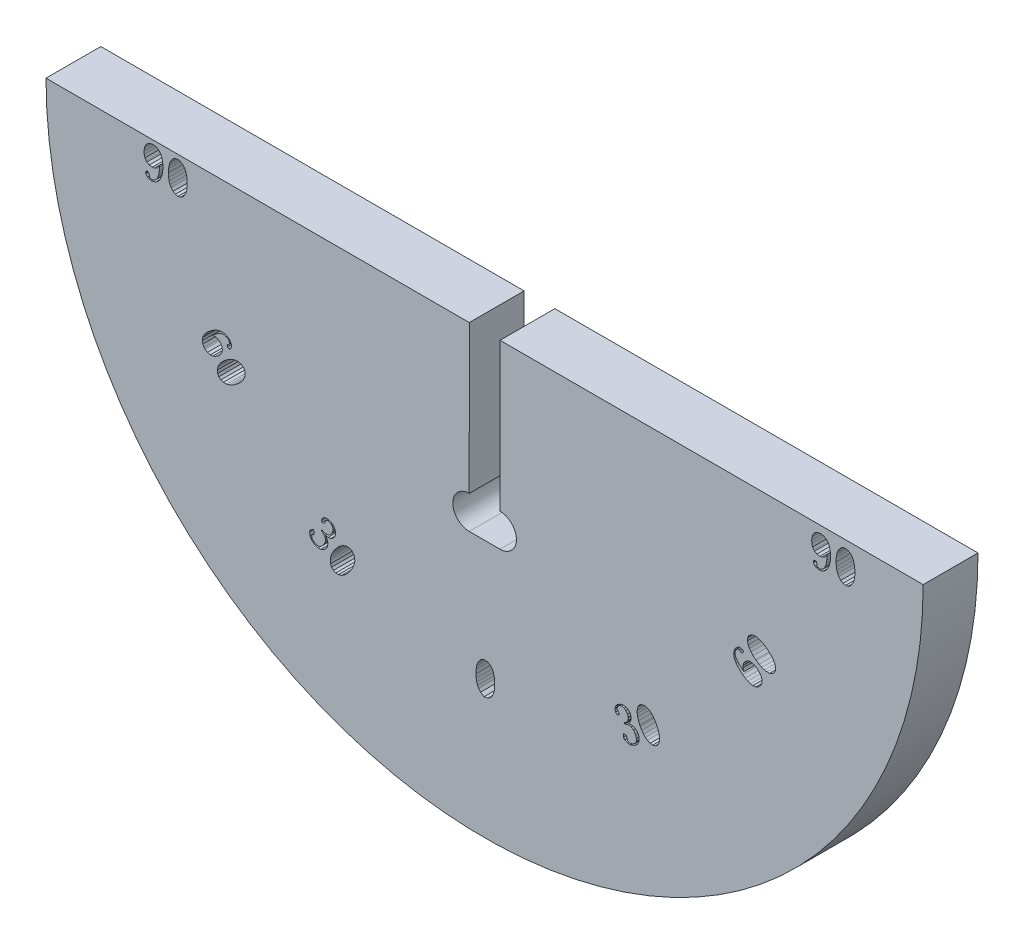
SolidWorks part; units mm, degrees
ref_plane "前视基准面" through (0, 0, 0) normal (0, 0, 1) x (1, 0, 0)
ref_plane "上视基准面" through (0, 0, 0) normal (0, 1, 0) x (1, 0, 0)
ref_plane "右视基准面" through (0, 0, 0) normal (1, 0, 0) x (0, 0, -1)
sketch "草图2" plane through (0, 0, 0) normal (0, 0, 1) x (1, 0, 0)
  line L0 (2575.9105, 4726.7519) -> (2576.0773, 4726.9587)
  line L1 (2576.0773, 4726.9587) -> (2576.1876, 4727.1913)
  line L2 (2576.1876, 4727.1913) -> (2576.2103, 4727.3332)
  line L3 (2576.2103, 4727.3332) -> (2576.169, 4727.5745)
  line L4 (2576.169, 4727.5745) -> (2576.024, 4727.8109)
  line L5 (2576.024, 4727.8109) -> (2575.9424, 4727.8993)
  line L6 (2575.9424, 4727.8993) -> (2575.7171, 4728.0289)
  line L7 (2575.7171, 4728.0289) -> (2575.5458, 4728.0673)
  line L8 (2575.5458, 4728.0673) -> (2575.2788, 4728.0401)
  line L9 (2575.2788, 4728.0401) -> (2575.4114, 4728.1448)
  line L10 (2575.4114, 4728.1448) -> (2575.6813, 4728.3434)
  line L11 (2575.6813, 4728.3434) -> (2575.9216, 4728.487)
  line L12 (2575.9216, 4728.487) -> (2576.1176, 4728.5721)
  line L13 (2576.1176, 4728.5721) -> (2576.2838, 4728.602)
  line L14 (2576.2838, 4728.602) -> (2576.3637, 4728.6027)
  line L15 (2576.3637, 4728.6027) -> (2576.6101, 4728.5404)
  line L16 (2576.6101, 4728.5404) -> (2576.8067, 4728.3818)
  line L17 (2576.8067, 4728.3818) -> (2576.8836, 4728.2111)
  line L18 (2576.8836, 4728.2111) -> (2576.8363, 4728.1095)
  line L19 (2576.8363, 4728.1095) -> (2576.7848, 4728.0671)
  line L20 (2576.7848, 4728.0671) -> (2576.7111, 4728.0242)
  line L21 (2576.7111, 4728.0242) -> (2576.6429, 4727.9261)
  line L22 (2576.6429, 4727.9261) -> (2576.6846, 4727.7908)
  line L23 (2576.6846, 4727.7908) -> (2576.8089, 4727.7216)
  line L24 (2576.8089, 4727.7216) -> (2576.9452, 4727.7895)
  line L25 (2576.9452, 4727.7895) -> (2576.9559, 4727.7943)
  line L26 (2576.9559, 4727.7943) -> (2577.0444, 4728.0395)
  line L27 (2577.0444, 4728.0395) -> (2577.0279, 4728.183)
  line L28 (2577.0279, 4728.183) -> (2576.9052, 4728.4198)
  line L29 (2576.9052, 4728.4198) -> (2576.8236, 4728.5082)
  line L30 (2576.8236, 4728.5082) -> (2576.6226, 4728.6551)
  line L31 (2576.6226, 4728.6551) -> (2576.3874, 4728.7354)
  line L32 (2576.3874, 4728.7354) -> (2576.1181, 4728.7489)
  line L33 (2576.1181, 4728.7489) -> (2575.9718, 4728.7246)
  line L34 (2575.9718, 4728.7246) -> (2575.7478, 4728.659)
  line L35 (2575.7478, 4728.659) -> (2575.513, 4728.5532)
  line L36 (2575.513, 4728.5532) -> (2575.2713, 4728.4058)
  line L37 (2575.2713, 4728.4058) -> (2575.0241, 4728.2206)
  line L38 (2575.0241, 4728.2206) -> (2574.8147, 4728.03)
  line L39 (2574.8147, 4728.03) -> (2574.6271, 4727.8267)
  line L40 (2574.6271, 4727.8267) -> (2574.4956, 4727.6198)
  line L41 (2574.4956, 4727.6198) -> (2574.4102, 4727.4176)
  line L42 (2574.4102, 4727.4176) -> (2574.4082, 4727.4007)
  line L43 (2574.4082, 4727.4007) -> (2574.3729, 4727.1441)
  line L44 (2574.3729, 4727.1441) -> (2574.4249, 4726.9075)
  line L45 (2574.4249, 4726.9075) -> (2574.5598, 4726.6794)
  line L46 (2574.5598, 4726.6794) -> (2574.639, 4726.5963)
  line L47 (2574.639, 4726.5963) -> (2574.8497, 4726.4634)
  line L48 (2574.8497, 4726.4634) -> (2575.113, 4726.3991)
  line L49 (2575.113, 4726.3991) -> (2575.1222, 4726.4)
  line L50 (2575.1222, 4726.4) -> (2575.3456, 4726.4172)
  line L51 (2575.3456, 4726.4172) -> (2575.5798, 4726.5099)
  line L52 (2575.5798, 4726.5099) -> (2575.8303, 4726.6805)
  line L53 (2575.8303, 4726.6805) -> (2575.9105, 4726.7519)
  line L54 (2574.6009, 4727.2666) -> (2574.7043, 4727.4699)
  line L55 (2574.7043, 4727.4699) -> (2574.862, 4727.6758)
  line L56 (2574.862, 4727.6758) -> (2575.0864, 4727.8828)
  line L57 (2575.0864, 4727.8828) -> (2575.3661, 4727.9318)
  line L58 (2575.3661, 4727.9318) -> (2575.5985, 4727.9145)
  line L59 (2575.5985, 4727.9145) -> (2575.6938, 4727.874)
  line L60 (2575.6938, 4727.874) -> (2575.8953, 4727.7048)
  line L61 (2575.8953, 4727.7048) -> (2575.9627, 4727.5907)
  line L62 (2575.9627, 4727.5907) -> (2575.9667, 4727.3325)
  line L63 (2575.9667, 4727.3325) -> (2575.9632, 4727.3117)
  line L64 (2575.9632, 4727.3117) -> (2575.8588, 4727.0946)
  line L65 (2575.8588, 4727.0946) -> (2575.662, 4726.8903)
  line L66 (2575.662, 4726.8903) -> (2575.4566, 4726.7336)
  line L67 (2575.4566, 4726.7336) -> (2575.2207, 4726.6017)
  line L68 (2575.2207, 4726.6017) -> (2575.0326, 4726.549)
  line L69 (2575.0326, 4726.549) -> (2574.8569, 4726.5757)
  line L70 (2574.8569, 4726.5757) -> (2574.6496, 4726.7295)
  line L71 (2574.6496, 4726.7295) -> (2574.6284, 4726.7552)
  line L72 (2574.6284, 4726.7552) -> (2574.5497, 4726.9798)
  line L73 (2574.5497, 4726.9798) -> (2574.6009, 4727.2666)
  line L74 (2575.9736, 4725.1533) -> (2575.9249, 4725.3879)
  line L75 (2575.9249, 4725.3879) -> (2576.0096, 4725.67)
  line L76 (2576.0096, 4725.67) -> (2576.0968, 4725.8184)
  line L77 (2576.0968, 4725.8184) -> (2576.2408, 4726.0117)
  line L78 (2576.2408, 4726.0117) -> (2576.4323, 4726.2135)
  line L79 (2576.4323, 4726.2135) -> (2576.666, 4726.4215)
  line L80 (2576.666, 4726.4215) -> (2576.8457, 4726.557)
  line L81 (2576.8457, 4726.557) -> (2577.0811, 4726.7112)
  line L82 (2577.0811, 4726.7112) -> (2577.3072, 4726.8292)
  line L83 (2577.3072, 4726.8292) -> (2577.5211, 4726.9031)
  line L84 (2577.5211, 4726.9031) -> (2577.5885, 4726.9174)
  line L85 (2577.5885, 4726.9174) -> (2577.8651, 4726.9232)
  line L86 (2577.8651, 4726.9232) -> (2578.0454, 4726.8151)
  line L87 (2578.0454, 4726.8151) -> (2578.0873, 4726.7505)
  line L88 (2578.0873, 4726.7505) -> (2578.1321, 4726.53)
  line L89 (2578.1321, 4726.53) -> (2578.0378, 4726.2692)
  line L90 (2578.0378, 4726.2692) -> (2577.9555, 4726.1455)
  line L91 (2577.9555, 4726.1455) -> (2577.7999, 4725.9566)
  line L92 (2577.7999, 4725.9566) -> (2577.6059, 4725.7601)
  line L93 (2577.6059, 4725.7601) -> (2577.3737, 4725.556)
  line L94 (2577.3737, 4725.556) -> (2577.179, 4725.4041)
  line L95 (2577.179, 4725.4041) -> (2576.9421, 4725.246)
  line L96 (2576.9421, 4725.246) -> (2576.7198, 4725.1266)
  line L97 (2576.7198, 4725.1266) -> (2576.5191, 4725.0522)
  line L98 (2576.5191, 4725.0522) -> (2576.4449, 4725.0316)
  line L99 (2576.4449, 4725.0316) -> (2576.1775, 4725.0267)
  line L100 (2576.1775, 4725.0267) -> (2575.9736, 4725.1533)
  line L101 (2578.1501, 4726.8968) -> (2577.9595, 4727.0556)
  line L102 (2577.9595, 4727.0556) -> (2577.7267, 4727.1305)
  line L103 (2577.7267, 4727.1305) -> (2577.4487, 4727.1208)
  line L104 (2577.4487, 4727.1208) -> (2577.4172, 4727.1194)
  line L105 (2577.4172, 4727.1194) -> (2577.1884, 4727.0645)
  line L106 (2577.1884, 4727.0645) -> (2576.9565, 4726.9664)
  line L107 (2576.9565, 4726.9664) -> (2576.7192, 4726.8306)
  line L108 (2576.7192, 4726.8306) -> (2576.4788, 4726.6517)
  line L109 (2576.4788, 4726.6517) -> (2576.4099, 4726.5982)
  line L110 (2576.4099, 4726.5982) -> (2576.1893, 4726.3897)
  line L111 (2576.1893, 4726.3897) -> (2576.0147, 4726.1858)
  line L112 (2576.0147, 4726.1858) -> (2575.8832, 4725.979)
  line L113 (2575.8832, 4725.979) -> (2575.7963, 4725.7729)
  line L114 (2575.7963, 4725.7729) -> (2575.7451, 4725.5091)
  line L115 (2575.7451, 4725.5091) -> (2575.7757, 4725.2629)
  line L116 (2575.7757, 4725.2629) -> (2575.8918, 4725.0552)
  line L117 (2575.8918, 4725.0552) -> (2576.0729, 4724.9025)
  line L118 (2576.0729, 4724.9025) -> (2576.3057, 4724.8276)
  line L119 (2576.3057, 4724.8276) -> (2576.59, 4724.8306)
  line L120 (2576.59, 4724.8306) -> (2576.6283, 4724.8382)
  line L121 (2576.6283, 4724.8382) -> (2576.8494, 4724.8961)
  line L122 (2576.8494, 4724.8961) -> (2577.0774, 4724.9956)
  line L123 (2577.0774, 4724.9956) -> (2577.3176, 4725.1391)
  line L124 (2577.3176, 4725.1391) -> (2577.5648, 4725.3243)
  line L125 (2577.5648, 4725.3243) -> (2577.6095, 4725.3605)
  line L126 (2577.6095, 4725.3605) -> (2577.8339, 4725.5675)
  line L127 (2577.8339, 4725.5675) -> (2578.0138, 4725.7738)
  line L128 (2578.0138, 4725.7738) -> (2578.1477, 4725.9753)
  line L129 (2578.1477, 4725.9753) -> (2578.2424, 4726.1784)
  line L130 (2578.2424, 4726.1784) -> (2578.2951, 4726.4461)
  line L131 (2578.2951, 4726.4461) -> (2578.2629, 4726.6884)
  line L132 (2578.2629, 4726.6884) -> (2578.1501, 4726.8968)
  line L133 (2560.123, 4740.7565) -> (2640.123, 4740.7565)
  line L134 (2600.123, 4722.8084) -> (2600.123, 4716.8788)
  line L135 (2601.5305, 4740.7565) -> (2601.523, 4727.2576)
  line L136 (2598.7261, 4740.7565) -> (2598.723, 4727.2576)
  line L137 (2560.123, 4740.7565) -> (2570.123, 4740.7565)
  line L138 (2560.7307, 4733.8105) -> (2570.5787, 4735.547)
  line L139 (2562.5353, 4727.0757) -> (2571.9322, 4730.4959)
  line L140 (2565.482, 4720.7565) -> (2574.1422, 4725.7565)
  line L141 (2569.4812, 4715.045) -> (2577.1416, 4721.4728)
  line L142 (2574.4115, 4710.1147) -> (2580.8394, 4717.7751)
  line L143 (2580.123, 4706.1155) -> (2585.123, 4714.7757)
  line L144 (2586.4422, 4703.1688) -> (2589.8624, 4712.5657)
  line L145 (2593.1771, 4701.3642) -> (2594.9135, 4711.2122)
  line L146 (2600.123, 4700.7565) -> (2600.123, 4710.7565)
  line L147 (2607.0689, 4701.3642) -> (2605.3324, 4711.2122)
  line L148 (2613.6331, 4703.6378) -> (2610.3836, 4712.5657)
  line L149 (2620.123, 4706.1155) -> (2615.123, 4714.7757)
  line L150 (2625.8345, 4710.1147) -> (2619.4066, 4717.7751)
  line L151 (2630.7648, 4715.045) -> (2623.1043, 4721.4728)
  line L152 (2634.764, 4720.7565) -> (2626.1037, 4725.7565)
  line L153 (2637.7107, 4727.0757) -> (2628.3138, 4730.4959)
  line L154 (2639.5153, 4733.8105) -> (2629.6672, 4735.547)
  line L155 (2640.123, 4740.7565) -> (2630.123, 4740.7565)
  line L156 (2560.123, 4740.7565) -> (2565.123, 4740.7565)
  line L157 (2560.1473, 4739.3605) -> (2565.1443, 4739.535)
  line L158 (2560.2204, 4737.9662) -> (2565.2082, 4738.315)
  line L159 (2560.3421, 4736.5753) -> (2565.3147, 4737.098)
  line L160 (2560.5123, 4735.1895) -> (2565.4636, 4735.8854)
  line L161 (2560.7307, 4733.8105) -> (2565.6547, 4734.6788)
  line L162 (2560.9971, 4732.44) -> (2565.8878, 4733.4796)
  line L163 (2561.3112, 4731.0796) -> (2566.1626, 4732.2892)
  line L164 (2561.6725, 4729.731) -> (2566.4788, 4731.1092)
  line L165 (2562.0807, 4728.3958) -> (2566.836, 4729.9409)
  line L166 (2562.5353, 4727.0757) -> (2567.2337, 4728.7858)
  line L167 (2563.0356, 4725.7722) -> (2567.6715, 4727.6452)
  line L168 (2563.5812, 4724.487) -> (2568.1489, 4726.5207)
  line L169 (2564.1712, 4723.2216) -> (2568.6652, 4725.4135)
  line L170 (2564.8051, 4721.9776) -> (2569.2198, 4724.325)
  line L171 (2565.482, 4720.7565) -> (2569.8121, 4723.2565)
  line L172 (2566.2011, 4719.5597) -> (2570.4413, 4722.2093)
  line L173 (2566.9615, 4718.3888) -> (2571.1067, 4721.1847)
  line L174 (2567.7623, 4717.2451) -> (2571.8074, 4720.184)
  line L175 (2568.6025, 4716.13) -> (2572.5426, 4719.2083)
  line L176 (2569.4812, 4715.045) -> (2573.3114, 4718.2589)
  line L177 (2570.3972, 4713.9912) -> (2574.1129, 4717.3369)
  line L178 (2571.3494, 4712.9701) -> (2574.9461, 4716.4434)
  line L179 (2572.3366, 4711.9829) -> (2575.8099, 4715.5796)
  line L180 (2573.3578, 4711.0307) -> (2576.7034, 4714.7464)
  line L181 (2574.4115, 4710.1147) -> (2577.6254, 4713.9449)
  line L182 (2575.4965, 4709.236) -> (2578.5748, 4713.1761)
  line L183 (2576.6116, 4708.3958) -> (2579.5505, 4712.4409)
  line L184 (2577.7553, 4707.595) -> (2580.5512, 4711.7402)
  line L185 (2578.9262, 4706.8346) -> (2581.5758, 4711.0748)
  line L186 (2580.123, 4706.1155) -> (2582.623, 4710.4456)
  line L187 (2581.3441, 4705.4386) -> (2583.6915, 4709.8533)
  line L188 (2582.5881, 4704.8047) -> (2584.78, 4709.2987)
  line L189 (2583.8535, 4704.2147) -> (2585.8872, 4708.7824)
  line L190 (2585.1387, 4703.6691) -> (2587.0117, 4708.305)
  line L191 (2586.4422, 4703.1688) -> (2588.1523, 4707.8672)
  line L192 (2587.7623, 4702.7142) -> (2589.3074, 4707.4695)
  line L193 (2589.0975, 4702.306) -> (2590.4757, 4707.1123)
  line L194 (2590.4461, 4701.9446) -> (2591.6557, 4706.7961)
  line L195 (2591.8065, 4701.6306) -> (2592.8461, 4706.5213)
  line L196 (2593.1771, 4701.3642) -> (2594.0453, 4706.2882)
  line L197 (2594.5561, 4701.1458) -> (2595.2519, 4706.0971)
  line L198 (2595.9418, 4700.9756) -> (2596.4645, 4705.9482)
  line L199 (2597.3327, 4700.8539) -> (2597.6815, 4705.8417)
  line L200 (2598.727, 4700.7808) -> (2598.9015, 4705.7778)
  line L201 (2600.123, 4700.7565) -> (2600.123, 4705.7565)
  line L202 (2601.519, 4700.7808) -> (2601.3445, 4705.7778)
  line L203 (2602.9132, 4700.8539) -> (2602.5645, 4705.8417)
  line L204 (2604.3041, 4700.9756) -> (2603.7815, 4705.9482)
  line L205 (2605.6899, 4701.1458) -> (2604.994, 4706.0971)
  line L206 (2607.0689, 4701.3642) -> (2606.2007, 4706.2882)
  line L207 (2608.4394, 4701.6306) -> (2607.3999, 4706.5213)
  line L208 (2609.7999, 4701.9446) -> (2608.5902, 4706.7961)
  line L209 (2611.1485, 4702.306) -> (2609.7703, 4707.1123)
  line L210 (2612.4837, 4702.7142) -> (2610.9386, 4707.4695)
  line L211 (2613.6331, 4703.6378) -> (2612.0937, 4707.8672)
  line L212 (2614.97, 4704.0571) -> (2613.2342, 4708.305)
  line L213 (2616.2208, 4704.6812) -> (2614.3588, 4708.7824)
  line L214 (2617.6578, 4704.8047) -> (2615.466, 4709.2987)
  line L215 (2618.9018, 4705.4386) -> (2616.5545, 4709.8533)
  line L216 (2620.123, 4706.1155) -> (2617.623, 4710.4456)
  line L217 (2621.3198, 4706.8346) -> (2618.6702, 4711.0748)
  line L218 (2622.4907, 4707.595) -> (2619.6947, 4711.7402)
  line L219 (2623.6344, 4708.3958) -> (2620.6955, 4712.4409)
  line L220 (2624.7494, 4709.236) -> (2621.6711, 4713.1761)
  line L221 (2625.8345, 4710.1147) -> (2622.6205, 4713.9449)
  line L222 (2626.8882, 4711.0307) -> (2623.5426, 4714.7464)
  line L223 (2627.9093, 4711.9829) -> (2624.436, 4715.5796)
  line L224 (2628.8966, 4712.9701) -> (2625.2999, 4716.4434)
  line L225 (2629.8488, 4713.9912) -> (2626.133, 4717.3369)
  line L226 (2630.7648, 4715.045) -> (2626.9345, 4718.2589)
  line L227 (2631.6434, 4716.13) -> (2627.7034, 4719.2083)
  line L228 (2632.4837, 4717.2451) -> (2628.4386, 4720.184)
  line L229 (2633.2845, 4718.3888) -> (2629.1393, 4721.1847)
  line L230 (2634.0449, 4719.5597) -> (2629.8047, 4722.2093)
  line L231 (2634.764, 4720.7565) -> (2630.4339, 4723.2565)
  line L232 (2635.4409, 4721.9776) -> (2631.0261, 4724.325)
  line L233 (2636.0747, 4723.2216) -> (2631.5808, 4725.4135)
  line L234 (2636.6648, 4724.487) -> (2632.0971, 4726.5207)
  line L235 (2637.2103, 4725.7722) -> (2632.5744, 4727.6452)
  line L236 (2637.7107, 4727.0757) -> (2633.0122, 4728.7858)
  line L237 (2638.1652, 4728.3958) -> (2633.41, 4729.9409)
  line L238 (2638.5734, 4729.731) -> (2633.7671, 4731.1092)
  line L239 (2638.9348, 4731.0796) -> (2634.0833, 4732.2892)
  line L240 (2639.2489, 4732.44) -> (2634.3581, 4733.4796)
  line L241 (2639.5153, 4733.8105) -> (2634.5913, 4734.6788)
  line L242 (2639.7337, 4735.1895) -> (2634.7824, 4735.8854)
  line L243 (2639.9039, 4736.5753) -> (2634.9312, 4737.098)
  line L244 (2640.0255, 4737.9662) -> (2635.0377, 4738.315)
  line L245 (2640.0986, 4739.3605) -> (2635.1017, 4739.535)
  line L246 (2640.123, 4740.7565) -> (2635.123, 4740.7565)
  line L247 (2572.133, 4737.564) -> (2571.9203, 4737.6796)
  line L248 (2571.9203, 4737.6796) -> (2571.7547, 4737.9238)
  line L249 (2571.7547, 4737.9238) -> (2571.6926, 4738.0811)
  line L250 (2571.6926, 4738.0811) -> (2571.6347, 4738.317)
  line L251 (2571.6347, 4738.317) -> (2571.6016, 4738.5901)
  line L252 (2571.6016, 4738.5901) -> (2571.5892, 4738.9046)
  line L253 (2571.5892, 4738.9046) -> (2571.5933, 4739.1281)
  line L254 (2571.5933, 4739.1281) -> (2571.6223, 4739.4095)
  line L255 (2571.6223, 4739.4095) -> (2571.6761, 4739.6578)
  line L256 (2571.6761, 4739.6578) -> (2571.7547, 4739.873)
  line L257 (2571.7547, 4739.873) -> (2571.7878, 4739.9351)
  line L258 (2571.7878, 4739.9351) -> (2571.9575, 4740.1503)
  line L259 (2571.9575, 4740.1503) -> (2572.1562, 4740.2207)
  line L260 (2572.1562, 4740.2207) -> (2572.2307, 4740.2165)
  line L261 (2572.2307, 4740.2165) -> (2572.4293, 4740.1089)
  line L262 (2572.4293, 4740.1089) -> (2572.57, 4739.873)
  line L263 (2572.57, 4739.873) -> (2572.6155, 4739.7282)
  line L264 (2572.6155, 4739.7282) -> (2572.6652, 4739.4882)
  line L265 (2572.6652, 4739.4882) -> (2572.6942, 4739.215)
  line L266 (2572.6942, 4739.215) -> (2572.7024, 4738.9046)
  line L267 (2572.7024, 4738.9046) -> (2572.6983, 4738.6605)
  line L268 (2572.6983, 4738.6605) -> (2572.6693, 4738.3749)
  line L269 (2572.6693, 4738.3749) -> (2572.6238, 4738.1266)
  line L270 (2572.6238, 4738.1266) -> (2572.5535, 4737.9238)
  line L271 (2572.5535, 4737.9238) -> (2572.5204, 4737.8534)
  line L272 (2572.5204, 4737.8534) -> (2572.3589, 4737.6424)
  line L273 (2572.3589, 4737.6424) -> (2572.133, 4737.564)
  line L274 (2572.9861, 4738.4492) -> (2573.0046, 4738.9046)
  line L275 (2573.0046, 4738.9046) -> (2573.0046, 4738.9667)
  line L276 (2573.0046, 4738.9667) -> (2572.9839, 4739.2688)
  line L277 (2572.9839, 4739.2688) -> (2572.9383, 4739.5378)
  line L278 (2572.9383, 4739.5378) -> (2572.868, 4739.7737)
  line L279 (2572.868, 4739.7737) -> (2572.7687, 4739.9724)
  line L280 (2572.7687, 4739.9724) -> (2572.5948, 4740.1793)
  line L281 (2572.5948, 4740.1793) -> (2572.3879, 4740.3117)
  line L282 (2572.3879, 4740.3117) -> (2572.1562, 4740.3573)
  line L283 (2572.1562, 4740.3573) -> (2572.1479, 4740.3573)
  line L284 (2572.1479, 4740.3573) -> (2571.912, 4740.3117)
  line L285 (2571.912, 4740.3117) -> (2571.7092, 4740.1752)
  line L286 (2571.7092, 4740.1752) -> (2571.5395, 4739.9558)
  line L287 (2571.5395, 4739.9558) -> (2571.523, 4739.9269)
  line L288 (2571.523, 4739.9269) -> (2571.4195, 4739.7158)
  line L289 (2571.4195, 4739.7158) -> (2571.345, 4739.4757)
  line L290 (2571.345, 4739.4757) -> (2571.3036, 4739.2067)
  line L291 (2571.3036, 4739.2067) -> (2571.2871, 4738.9046)
  line L292 (2571.2871, 4738.9046) -> (2571.2912, 4738.8177)
  line L293 (2571.2912, 4738.8177) -> (2571.3119, 4738.5156)
  line L294 (2571.3119, 4738.5156) -> (2571.3574, 4738.2507)
  line L295 (2571.3574, 4738.2507) -> (2571.4361, 4738.019)
  line L296 (2571.4361, 4738.019) -> (2571.5395, 4737.8245)
  line L297 (2571.5395, 4737.8245) -> (2571.7133, 4737.6134)
  line L298 (2571.7133, 4737.6134) -> (2571.9203, 4737.4851)
  line L299 (2571.9203, 4737.4851) -> (2572.1562, 4737.4396)
  line L300 (2572.1562, 4737.4396) -> (2572.3879, 4737.4851)
  line L301 (2572.3879, 4737.4851) -> (2572.5907, 4737.6175)
  line L302 (2572.5907, 4737.6175) -> (2572.7687, 4737.841)
  line L303 (2572.7687, 4737.841) -> (2572.7894, 4737.8741)
  line L304 (2572.7894, 4737.8741) -> (2572.8845, 4738.0811)
  line L305 (2572.8845, 4738.0811) -> (2572.9861, 4738.4492)
  line L306 (2584.4854, 4717.3007) -> (2584.2298, 4717.1204)
  line L307 (2584.2298, 4717.1204) -> (2584.1619, 4716.951)
  line L308 (2584.1619, 4716.951) -> (2584.1896, 4716.6819)
  line L309 (2584.1896, 4716.6819) -> (2584.1972, 4716.6568)
  line L310 (2584.1972, 4716.6568) -> (2584.319, 4716.4338)
  line L311 (2584.319, 4716.4338) -> (2584.519, 4716.2508)
  line L312 (2584.519, 4716.2508) -> (2584.6998, 4716.1453)
  line L313 (2584.6998, 4716.1453) -> (2584.9418, 4716.0679)
  line L314 (2584.9418, 4716.0679) -> (2585.1828, 4716.0707)
  line L315 (2585.1828, 4716.0707) -> (2585.2922, 4716.1023)
  line L316 (2585.2922, 4716.1023) -> (2585.5234, 4716.2198)
  line L317 (2585.5234, 4716.2198) -> (2585.6977, 4716.4035)
  line L318 (2585.6977, 4716.4035) -> (2585.7809, 4716.5584)
  line L319 (2585.7809, 4716.5584) -> (2585.8291, 4716.8203)
  line L320 (2585.8291, 4716.8203) -> (2585.8258, 4716.904)
  line L321 (2585.8258, 4716.904) -> (2585.7646, 4717.1344)
  line L322 (2585.7646, 4717.1344) -> (2585.6165, 4717.3946)
  line L323 (2585.6165, 4717.3946) -> (2585.8554, 4717.3503)
  line L324 (2585.8554, 4717.3503) -> (2586.099, 4717.3854)
  line L325 (2586.099, 4717.3854) -> (2586.2574, 4717.4769)
  line L326 (2586.2574, 4717.4769) -> (2586.4428, 4717.6735)
  line L327 (2586.4428, 4717.6735) -> (2586.5248, 4717.8731)
  line L328 (2586.5248, 4717.8731) -> (2586.5245, 4718.1464)
  line L329 (2586.5245, 4718.1464) -> (2586.5124, 4718.2138)
  line L330 (2586.5124, 4718.2138) -> (2586.4031, 4718.4406)
  line L331 (2586.4031, 4718.4406) -> (2586.2123, 4718.625)
  line L332 (2586.2123, 4718.625) -> (2586.2065, 4718.626)
  line L333 (2586.2065, 4718.626) -> (2585.9691, 4718.7473)
  line L334 (2585.9691, 4718.7473) -> (2585.7143, 4718.7853)
  line L335 (2585.7143, 4718.7853) -> (2585.4883, 4718.7323)
  line L336 (2585.4883, 4718.7323) -> (2585.2997, 4718.5689)
  line L337 (2585.2997, 4718.5689) -> (2585.2496, 4718.3816)
  line L338 (2585.2496, 4718.3816) -> (2585.3167, 4718.272)
  line L339 (2585.3167, 4718.272) -> (2585.4402, 4718.2477)
  line L340 (2585.4402, 4718.2477) -> (2585.5447, 4718.3365)
  line L341 (2585.5447, 4718.3365) -> (2585.563, 4718.4254)
  line L342 (2585.563, 4718.4254) -> (2585.64, 4718.5962)
  line L343 (2585.64, 4718.5962) -> (2585.8551, 4718.6719)
  line L344 (2585.8551, 4718.6719) -> (2586.1009, 4718.5819)
  line L345 (2586.1009, 4718.5819) -> (2586.2353, 4718.4488)
  line L346 (2586.2353, 4718.4488) -> (2586.3103, 4718.2131)
  line L347 (2586.3103, 4718.2131) -> (2586.2814, 4718.0459)
  line L348 (2586.2814, 4718.0459) -> (2586.1684, 4717.8041)
  line L349 (2586.1684, 4717.8041) -> (2586.0042, 4717.6275)
  line L350 (2586.0042, 4717.6275) -> (2585.7866, 4717.5196)
  line L351 (2585.7866, 4717.5196) -> (2585.7808, 4717.5206)
  line L352 (2585.7808, 4717.5206) -> (2585.5462, 4717.5374)
  line L353 (2585.5462, 4717.5374) -> (2585.2938, 4717.6582)
  line L354 (2585.2938, 4717.6582) -> (2585.2385, 4717.5787)
  line L355 (2585.2385, 4717.5787) -> (2585.3616, 4717.4832)
  line L356 (2585.3616, 4717.4832) -> (2585.5471, 4717.2848)
  line L357 (2585.5471, 4717.2848) -> (2585.6257, 4717.0871)
  line L358 (2585.6257, 4717.0871) -> (2585.5964, 4716.8486)
  line L359 (2585.5964, 4716.8486) -> (2585.4708, 4716.6031)
  line L360 (2585.4708, 4716.6031) -> (2585.4276, 4716.5422)
  line L361 (2585.4276, 4716.5422) -> (2585.2321, 4716.3384)
  line L362 (2585.2321, 4716.3384) -> (2585.0361, 4716.2357)
  line L363 (2585.0361, 4716.2357) -> (2584.8008, 4716.2318)
  line L364 (2584.8008, 4716.2318) -> (2584.5485, 4716.3526)
  line L365 (2584.5485, 4716.3526) -> (2584.538, 4716.3604)
  line L366 (2584.538, 4716.3604) -> (2584.3674, 4716.5591)
  line L367 (2584.3674, 4716.5591) -> (2584.3537, 4716.7723)
  line L368 (2584.3537, 4716.7723) -> (2584.4471, 4716.8483)
  line L369 (2584.4471, 4716.8483) -> (2584.5603, 4716.9534)
  line L370 (2584.5603, 4716.9534) -> (2584.5975, 4717.0658)
  line L371 (2584.5975, 4717.0658) -> (2584.4854, 4717.3007)
  line L372 (2587.5338, 4717.4909) -> (2587.2663, 4717.4035)
  line L373 (2587.2663, 4717.4035) -> (2587.2378, 4717.3935)
  line L374 (2587.2378, 4717.3935) -> (2587.0331, 4717.2745)
  line L375 (2587.0331, 4717.2745) -> (2586.834, 4717.1188)
  line L376 (2586.834, 4717.1188) -> (2586.6486, 4716.9222)
  line L377 (2586.6486, 4716.9222) -> (2586.4619, 4716.6842)
  line L378 (2586.4619, 4716.6842) -> (2586.4143, 4716.6152)
  line L379 (2586.4143, 4716.6152) -> (2586.2593, 4716.3539)
  line L380 (2586.2593, 4716.3539) -> (2586.1453, 4716.1064)
  line L381 (2586.1453, 4716.1064) -> (2586.0756, 4715.8749)
  line L382 (2586.0756, 4715.8749) -> (2586.0492, 4715.6537)
  line L383 (2586.0492, 4715.6537) -> (2586.0736, 4715.3823)
  line L384 (2586.0736, 4715.3823) -> (2586.1714, 4715.1575)
  line L385 (2586.1714, 4715.1575) -> (2586.3378, 4714.9862)
  line L386 (2586.3378, 4714.9862) -> (2586.5527, 4714.8896)
  line L387 (2586.5527, 4714.8896) -> (2586.7985, 4714.8858)
  line L388 (2586.7985, 4714.8858) -> (2587.0732, 4714.963)
  line L389 (2587.0732, 4714.963) -> (2587.106, 4714.9811)
  line L390 (2587.106, 4714.9811) -> (2587.3016, 4715.0988)
  line L391 (2587.3016, 4715.0988) -> (2587.495, 4715.2554)
  line L392 (2587.495, 4715.2554) -> (2587.6848, 4715.4602)
  line L393 (2587.6848, 4715.4602) -> (2587.8701, 4715.7073)
  line L394 (2587.8701, 4715.7073) -> (2587.9055, 4715.7577)
  line L395 (2587.9055, 4715.7577) -> (2588.0629, 4716.0155)
  line L396 (2588.0629, 4716.0155) -> (2588.1793, 4716.2597)
  line L397 (2588.1793, 4716.2597) -> (2588.2558, 4716.496)
  line L398 (2588.2558, 4716.496) -> (2588.2879, 4716.7161)
  line L399 (2588.2879, 4716.7161) -> (2588.2659, 4716.9842)
  line L400 (2588.2659, 4716.9842) -> (2588.1715, 4717.2114)
  line L401 (2588.1715, 4717.2114) -> (2588.0018, 4717.3803)
  line L402 (2588.0018, 4717.3803) -> (2587.997, 4717.3871)
  line L403 (2587.997, 4717.3871) -> (2587.7786, 4717.4813)
  line L404 (2587.7786, 4717.4813) -> (2587.5338, 4717.4909)
  line L405 (2586.3881, 4715.1017) -> (2586.282, 4715.3165)
  line L406 (2586.282, 4715.3165) -> (2586.2857, 4715.6129)
  line L407 (2586.2857, 4715.6129) -> (2586.3227, 4715.7758)
  line L408 (2586.3227, 4715.7758) -> (2586.4097, 4716.0042)
  line L409 (2586.4097, 4716.0042) -> (2586.5411, 4716.2488)
  line L410 (2586.5411, 4716.2488) -> (2586.7087, 4716.5139)
  line L411 (2586.7087, 4716.5139) -> (2586.8406, 4716.693)
  line L412 (2586.8406, 4716.693) -> (2587.0266, 4716.9103)
  line L413 (2587.0266, 4716.9103) -> (2587.2105, 4717.0805)
  line L414 (2587.2105, 4717.0805) -> (2587.3965, 4717.2117)
  line L415 (2587.3965, 4717.2117) -> (2587.4587, 4717.2455)
  line L416 (2587.4587, 4717.2455) -> (2587.7219, 4717.3247)
  line L417 (2587.7219, 4717.3247) -> (2587.9265, 4717.2716)
  line L418 (2587.9265, 4717.2716) -> (2587.984, 4717.226)
  line L419 (2587.984, 4717.226) -> (2588.0857, 4717.0243)
  line L420 (2588.0857, 4717.0243) -> (2588.0677, 4716.7482)
  line L421 (2588.0677, 4716.7482) -> (2588.0221, 4716.6047)
  line L422 (2588.0221, 4716.6047) -> (2587.9236, 4716.3782)
  line L423 (2587.9236, 4716.3782) -> (2587.7956, 4716.136)
  line L424 (2587.7956, 4716.136) -> (2587.6233, 4715.8777)
  line L425 (2587.6233, 4715.8777) -> (2587.4792, 4715.6799)
  line L426 (2587.4792, 4715.6799) -> (2587.2956, 4715.4592)
  line L427 (2587.2956, 4715.4592) -> (2587.1141, 4715.2856)
  line L428 (2587.1141, 4715.2856) -> (2586.943, 4715.1548)
  line L429 (2586.943, 4715.1548) -> (2586.874, 4715.1162)
  line L430 (2586.874, 4715.1162) -> (2586.62, 4715.0384)
  line L431 (2586.62, 4715.0384) -> (2586.3881, 4715.1017)
  line L432 (2569.9145, 4740.2927) -> (2570.1783, 4740.2279)
  line L433 (2570.1783, 4740.2279) -> (2570.348, 4740.0582)
  line L434 (2570.348, 4740.0582) -> (2570.3977, 4739.9465)
  line L435 (2570.3977, 4739.9465) -> (2570.4597, 4739.6981)
  line L436 (2570.4597, 4739.6981) -> (2570.4804, 4739.4085)
  line L437 (2570.4804, 4739.4085) -> (2570.4432, 4739.2181)
  line L438 (2570.4432, 4739.2181) -> (2570.2983, 4738.9739)
  line L439 (2570.2983, 4738.9739) -> (2570.2942, 4738.9698)
  line L440 (2570.2942, 4738.9698) -> (2570.0831, 4738.7959)
  line L441 (2570.0831, 4738.7959) -> (2569.8514, 4738.7421)
  line L442 (2569.8514, 4738.7421) -> (2569.6858, 4738.7711)
  line L443 (2569.6858, 4738.7711) -> (2569.483, 4738.9408)
  line L444 (2569.483, 4738.9408) -> (2569.4541, 4738.978)
  line L445 (2569.4541, 4738.978) -> (2569.363, 4739.1974)
  line L446 (2569.363, 4739.1974) -> (2569.334, 4739.4912)
  line L447 (2569.334, 4739.4912) -> (2569.334, 4739.5781)
  line L448 (2569.334, 4739.5781) -> (2569.3754, 4739.8471)
  line L449 (2569.3754, 4739.8471) -> (2569.4665, 4740.0748)
  line L450 (2569.4665, 4740.0748) -> (2569.6403, 4740.2362)
  line L451 (2569.6403, 4740.2362) -> (2569.9145, 4740.2927)
  line L452 (2570.7647, 4738.6627) -> (2570.7825, 4739.0898)
  line L453 (2570.7825, 4739.0898) -> (2570.7701, 4739.3505)
  line L454 (2570.7701, 4739.3505) -> (2570.7287, 4739.6278)
  line L455 (2570.7287, 4739.6278) -> (2570.6542, 4739.8637)
  line L456 (2570.6542, 4739.8637) -> (2570.5508, 4740.0582)
  line L457 (2570.5508, 4740.0582) -> (2570.377, 4740.2362)
  line L458 (2570.377, 4740.2362) -> (2570.1618, 4740.352)
  line L459 (2570.1618, 4740.352) -> (2569.901, 4740.3893)
  line L460 (2569.901, 4740.3893) -> (2569.7065, 4740.3727)
  line L461 (2569.7065, 4740.3727) -> (2569.4706, 4740.2858)
  line L462 (2569.4706, 4740.2858) -> (2569.2844, 4740.1244)
  line L463 (2569.2844, 4740.1244) -> (2569.1851, 4739.9713)
  line L464 (2569.1851, 4739.9713) -> (2569.0982, 4739.7313)
  line L465 (2569.0982, 4739.7313) -> (2569.065, 4739.4581)
  line L466 (2569.065, 4739.4581) -> (2569.0816, 4739.2264)
  line L467 (2569.0816, 4739.2264) -> (2569.1478, 4738.9739)
  line L468 (2569.1478, 4738.9739) -> (2569.2678, 4738.7918)
  line L469 (2569.2678, 4738.7918) -> (2569.3299, 4738.7297)
  line L470 (2569.3299, 4738.7297) -> (2569.5451, 4738.6138)
  line L471 (2569.5451, 4738.6138) -> (2569.8183, 4738.5725)
  line L472 (2569.8183, 4738.5725) -> (2570.0086, 4738.5973)
  line L473 (2570.0086, 4738.5973) -> (2570.2321, 4738.7049)
  line L474 (2570.2321, 4738.7049) -> (2570.3439, 4738.8166)
  line L475 (2570.3439, 4738.8166) -> (2570.4804, 4739.0401)
  line L476 (2570.4804, 4739.0401) -> (2570.4763, 4738.9035)
  line L477 (2570.4763, 4738.9035) -> (2570.4473, 4738.5807)
  line L478 (2570.4473, 4738.5807) -> (2570.4018, 4738.3076)
  line L479 (2570.4018, 4738.3076) -> (2570.3397, 4738.0841)
  line L480 (2570.3397, 4738.0841) -> (2570.2652, 4737.9062)
  line L481 (2570.2652, 4737.9062) -> (2570.1783, 4737.782)
  line L482 (2570.1783, 4737.782) -> (2569.9838, 4737.6247)
  line L483 (2569.9838, 4737.6247) -> (2569.7479, 4737.5751)
  line L484 (2569.7479, 4737.5751) -> (2569.6651, 4737.5916)
  line L485 (2569.6651, 4737.5916) -> (2569.5989, 4737.6082)
  line L486 (2569.5989, 4737.6082) -> (2569.5658, 4737.6744)
  line L487 (2569.5658, 4737.6744) -> (2569.5493, 4737.7737)
  line L488 (2569.5493, 4737.7737) -> (2569.5161, 4737.9558)
  line L489 (2569.5161, 4737.9558) -> (2569.3837, 4738.0386)
  line L490 (2569.3837, 4738.0386) -> (2569.2513, 4737.9724)
  line L491 (2569.2513, 4737.9724) -> (2569.2182, 4737.8399)
  line L492 (2569.2182, 4737.8399) -> (2569.2264, 4737.7696)
  line L493 (2569.2264, 4737.7696) -> (2569.3837, 4737.5751)
  line L494 (2569.3837, 4737.5751) -> (2569.483, 4737.5213)
  line L495 (2569.483, 4737.5213) -> (2569.7479, 4737.4716)
  line L496 (2569.7479, 4737.4716) -> (2569.9217, 4737.4882)
  line L497 (2569.9217, 4737.4882) -> (2570.1493, 4737.5709)
  line L498 (2570.1493, 4737.5709) -> (2570.348, 4737.7199)
  line L499 (2570.348, 4737.7199) -> (2570.5177, 4737.9393)
  line L500 (2570.5177, 4737.9393) -> (2570.5715, 4738.0469)
  line L501 (2570.5715, 4738.0469) -> (2570.6667, 4738.2703)
  line L502 (2570.6667, 4738.2703) -> (2570.7647, 4738.6627)
  line L503 (2600.1723, 4712.0304) -> (2599.9642, 4712.1435)
  line L504 (2599.9642, 4712.1435) -> (2599.7987, 4712.3877)
  line L505 (2599.7987, 4712.3877) -> (2599.7366, 4712.545)
  line L506 (2599.7366, 4712.545) -> (2599.6787, 4712.7809)
  line L507 (2599.6787, 4712.7809) -> (2599.6456, 4713.0582)
  line L508 (2599.6456, 4713.0582) -> (2599.6331, 4713.3727)
  line L509 (2599.6331, 4713.3727) -> (2599.6373, 4713.5962)
  line L510 (2599.6373, 4713.5962) -> (2599.6704, 4713.8776)
  line L511 (2599.6704, 4713.8776) -> (2599.7201, 4714.1259)
  line L512 (2599.7201, 4714.1259) -> (2599.7987, 4714.337)
  line L513 (2599.7987, 4714.337) -> (2599.8318, 4714.4032)
  line L514 (2599.8318, 4714.4032) -> (2600.0015, 4714.6184)
  line L515 (2600.0015, 4714.6184) -> (2600.2001, 4714.6888)
  line L516 (2600.2001, 4714.6888) -> (2600.2746, 4714.6805)
  line L517 (2600.2746, 4714.6805) -> (2600.4733, 4714.577)
  line L518 (2600.4733, 4714.577) -> (2600.614, 4714.337)
  line L519 (2600.614, 4714.337) -> (2600.6595, 4714.1963)
  line L520 (2600.6595, 4714.1963) -> (2600.7092, 4713.9562)
  line L521 (2600.7092, 4713.9562) -> (2600.7381, 4713.6789)
  line L522 (2600.7381, 4713.6789) -> (2600.7506, 4713.3727)
  line L523 (2600.7506, 4713.3727) -> (2600.7423, 4713.1244)
  line L524 (2600.7423, 4713.1244) -> (2600.7174, 4712.8388)
  line L525 (2600.7174, 4712.8388) -> (2600.6678, 4712.5946)
  line L526 (2600.6678, 4712.5946) -> (2600.5974, 4712.3877)
  line L527 (2600.5974, 4712.3877) -> (2600.5643, 4712.3174)
  line L528 (2600.5643, 4712.3174) -> (2600.4029, 4712.1104)
  line L529 (2600.4029, 4712.1104) -> (2600.1723, 4712.0304)
  line L530 (2600.0741, 4711.8787) -> (2600.4319, 4711.949)
  line L531 (2600.4319, 4711.949) -> (2600.6347, 4712.0856)
  line L532 (2600.6347, 4712.0856) -> (2600.8168, 4712.3049)
  line L533 (2600.8168, 4712.3049) -> (2600.8333, 4712.3381)
  line L534 (2600.8333, 4712.3381) -> (2600.9285, 4712.545)
  line L535 (2600.9285, 4712.545) -> (2600.9947, 4712.7892)
  line L536 (2600.9947, 4712.7892) -> (2601.0361, 4713.0623)
  line L537 (2601.0361, 4713.0623) -> (2601.0485, 4713.3727)
  line L538 (2601.0485, 4713.3727) -> (2601.0485, 4713.4306)
  line L539 (2601.0485, 4713.4306) -> (2601.0278, 4713.7327)
  line L540 (2601.0278, 4713.7327) -> (2600.9865, 4714.0018)
  line L541 (2600.9865, 4714.0018) -> (2600.912, 4714.2376)
  line L542 (2600.912, 4714.2376) -> (2600.8168, 4714.4404)
  line L543 (2600.8168, 4714.4404) -> (2600.643, 4714.6474)
  line L544 (2600.643, 4714.6474) -> (2600.4319, 4714.7798)
  line L545 (2600.4319, 4714.7798) -> (2600.2001, 4714.8212)
  line L546 (2600.2001, 4714.8212) -> (2600.1918, 4714.8212)
  line L547 (2600.1918, 4714.8212) -> (2599.956, 4714.7757)
  line L548 (2599.956, 4714.7757) -> (2599.7532, 4714.6432)
  line L549 (2599.7532, 4714.6432) -> (2599.5835, 4714.4239)
  line L550 (2599.5835, 4714.4239) -> (2599.5669, 4714.3949)
  line L551 (2599.5669, 4714.3949) -> (2599.4635, 4714.1838)
  line L552 (2599.4635, 4714.1838) -> (2599.3931, 4713.9397)
  line L553 (2599.3931, 4713.9397) -> (2599.3476, 4713.6707)
  line L554 (2599.3476, 4713.6707) -> (2599.3352, 4713.3727)
  line L555 (2599.3352, 4713.3727) -> (2599.3352, 4713.2858)
  line L556 (2599.3352, 4713.2858) -> (2599.3559, 4712.9837)
  line L557 (2599.3559, 4712.9837) -> (2599.4055, 4712.7188)
  line L558 (2599.4055, 4712.7188) -> (2599.48, 4712.487)
  line L559 (2599.48, 4712.487) -> (2599.5835, 4712.2884)
  line L560 (2599.5835, 4712.2884) -> (2599.7573, 4712.0815)
  line L561 (2599.7573, 4712.0815) -> (2600.0741, 4711.8787)
  line L562 (2598.723, 4724.2576) -> (2601.523, 4724.2576)
  line L563 (2612.7666, 4715.3328) -> (2612.7977, 4715.0216)
  line L564 (2612.7977, 4715.0216) -> (2612.9118, 4714.8791)
  line L565 (2612.9118, 4714.8791) -> (2613.1597, 4714.7708)
  line L566 (2613.1597, 4714.7708) -> (2613.1853, 4714.765)
  line L567 (2613.1853, 4714.765) -> (2613.4393, 4714.7613)
  line L568 (2613.4393, 4714.7613) -> (2613.6971, 4714.8453)
  line L569 (2613.6971, 4714.8453) -> (2613.8779, 4714.9508)
  line L570 (2613.8779, 4714.9508) -> (2614.0644, 4715.1233)
  line L571 (2614.0644, 4715.1233) -> (2614.1806, 4715.3346)
  line L572 (2614.1806, 4715.3346) -> (2614.2069, 4715.4453)
  line L573 (2614.2069, 4715.4453) -> (2614.2185, 4715.7044)
  line L574 (2614.2185, 4715.7044) -> (2614.1443, 4715.9465)
  line L575 (2614.1443, 4715.9465) -> (2614.0504, 4716.0952)
  line L576 (2614.0504, 4716.0952) -> (2613.8462, 4716.2661)
  line L577 (2613.8462, 4716.2661) -> (2613.7717, 4716.3043)
  line L578 (2613.7717, 4716.3043) -> (2613.541, 4716.3645)
  line L579 (2613.541, 4716.3645) -> (2613.2417, 4716.3636)
  line L580 (2613.2417, 4716.3636) -> (2613.3977, 4716.5498)
  line L581 (2613.3977, 4716.5498) -> (2613.4871, 4716.7792)
  line L582 (2613.4871, 4716.7792) -> (2613.4855, 4716.962)
  line L583 (2613.4855, 4716.962) -> (2613.4056, 4717.2202)
  line L584 (2613.4056, 4717.2202) -> (2613.2721, 4717.3899)
  line L585 (2613.2721, 4717.3899) -> (2613.0341, 4717.5241)
  line L586 (2613.0341, 4717.5241) -> (2612.9695, 4717.5468)
  line L587 (2612.9695, 4717.5468) -> (2612.7183, 4717.5632)
  line L588 (2612.7183, 4717.5632) -> (2612.4638, 4717.4879)
  line L589 (2612.4638, 4717.4879) -> (2612.4601, 4717.4833)
  line L590 (2612.4601, 4717.4833) -> (2612.2377, 4717.3363)
  line L591 (2612.2377, 4717.3363) -> (2612.0791, 4717.1333)
  line L592 (2612.0791, 4717.1333) -> (2612.0141, 4716.9105)
  line L593 (2612.0141, 4716.9105) -> (2612.0635, 4716.6659)
  line L594 (2612.0635, 4716.6659) -> (2612.2019, 4716.53)
  line L595 (2612.2019, 4716.53) -> (2612.3303, 4716.5345)
  line L596 (2612.3303, 4716.5345) -> (2612.4123, 4716.6301)
  line L597 (2612.4123, 4716.6301) -> (2612.3864, 4716.7647)
  line L598 (2612.3864, 4716.7647) -> (2612.318, 4716.8245)
  line L599 (2612.318, 4716.8245) -> (2612.2072, 4716.9756)
  line L600 (2612.2072, 4716.9756) -> (2612.2472, 4717.2)
  line L601 (2612.2472, 4717.2) -> (2612.4465, 4717.3697)
  line L602 (2612.4465, 4717.3697) -> (2612.6285, 4717.4212)
  line L603 (2612.6285, 4717.4212) -> (2612.8706, 4717.3705)
  line L604 (2612.8706, 4717.3705) -> (2613.002, 4717.263)
  line L605 (2613.002, 4717.263) -> (2613.1568, 4717.0456)
  line L606 (2613.1568, 4717.0456) -> (2613.2297, 4716.8158)
  line L607 (2613.2297, 4716.8158) -> (2613.2165, 4716.5733)
  line L608 (2613.2165, 4716.5733) -> (2613.2128, 4716.5687)
  line L609 (2613.2128, 4716.5687) -> (2613.0827, 4716.3727)
  line L610 (2613.0827, 4716.3727) -> (2612.8533, 4716.2125)
  line L611 (2612.8533, 4716.2125) -> (2612.8953, 4716.1252)
  line L612 (2612.8953, 4716.1252) -> (2613.0391, 4716.1853)
  line L613 (2613.0391, 4716.1853) -> (2613.303, 4716.2492)
  line L614 (2613.303, 4716.2492) -> (2613.5139, 4716.2203)
  line L615 (2613.5139, 4716.2203) -> (2613.707, 4716.0774)
  line L616 (2613.707, 4716.0774) -> (2613.859, 4715.8472)
  line L617 (2613.859, 4715.8472) -> (2613.8907, 4715.7797)
  line L618 (2613.8907, 4715.7797) -> (2613.9718, 4715.5092)
  line L619 (2613.9718, 4715.5092) -> (2613.9648, 4715.288)
  line L620 (2613.9648, 4715.288) -> (2613.8524, 4715.0813)
  line L621 (2613.8524, 4715.0813) -> (2613.623, 4714.9211)
  line L622 (2613.623, 4714.9211) -> (2613.6111, 4714.9158)
  line L623 (2613.6111, 4714.9158) -> (2613.3541, 4714.8651)
  line L624 (2613.3541, 4714.8651) -> (2613.1618, 4714.9582)
  line L625 (2613.1618, 4714.9582) -> (2613.1416, 4715.0768)
  line L626 (2613.1416, 4715.0768) -> (2613.1058, 4715.2271)
  line L627 (2613.1058, 4715.2271) -> (2613.0263, 4715.3148)
  line L628 (2613.0263, 4715.3148) -> (2612.7666, 4715.3328)
  line L629 (2614.1015, 4718.08) -> (2614.0459, 4717.8041)
  line L630 (2614.0459, 4717.8041) -> (2614.0406, 4717.7745)
  line L631 (2614.0406, 4717.7745) -> (2614.0434, 4717.5377)
  line L632 (2614.0434, 4717.5377) -> (2614.0809, 4717.2877)
  line L633 (2614.0809, 4717.2877) -> (2614.1608, 4717.0295)
  line L634 (2614.1608, 4717.0295) -> (2614.2761, 4716.7499)
  line L635 (2614.2761, 4716.7499) -> (2614.3128, 4716.6746)
  line L636 (2614.3128, 4716.6746) -> (2614.4639, 4716.411)
  line L637 (2614.4639, 4716.411) -> (2614.6233, 4716.1899)
  line L638 (2614.6233, 4716.1899) -> (2614.7905, 4716.0153)
  line L639 (2614.7905, 4716.0153) -> (2614.97, 4715.8835)
  line L640 (2614.97, 4715.8835) -> (2615.2183, 4715.7711)
  line L641 (2615.2183, 4715.7711) -> (2615.4621, 4715.7455)
  line L642 (2615.4621, 4715.7455) -> (2615.6931, 4715.8061)
  line L643 (2615.6931, 4715.8061) -> (2615.883, 4715.9457)
  line L644 (2615.883, 4715.9457) -> (2616.0073, 4716.1578)
  line L645 (2616.0073, 4716.1578) -> (2616.0753, 4716.4349)
  line L646 (2616.0753, 4716.4349) -> (2616.0757, 4716.4724)
  line L647 (2616.0757, 4716.4724) -> (2616.0695, 4716.7005)
  line L648 (2616.0695, 4716.7005) -> (2616.0283, 4716.9459)
  line L649 (2616.0283, 4716.9459) -> (2615.9435, 4717.212)
  line L650 (2615.9435, 4717.212) -> (2615.8195, 4717.4949)
  line L651 (2615.8195, 4717.4949) -> (2615.7932, 4717.5505)
  line L652 (2615.7932, 4717.5505) -> (2615.6462, 4717.8144)
  line L653 (2615.6462, 4717.8144) -> (2615.4909, 4718.036)
  line L654 (2615.4909, 4718.036) -> (2615.3229, 4718.2188)
  line L655 (2615.3229, 4718.2188) -> (2615.1471, 4718.3551)
  line L656 (2615.1471, 4718.3551) -> (2614.9029, 4718.468)
  line L657 (2614.9029, 4718.468) -> (2614.6587, 4718.4976)
  line L658 (2614.6587, 4718.4976) -> (2614.4281, 4718.433)
  line L659 (2614.4281, 4718.433) -> (2614.4198, 4718.4321)
  line L660 (2614.4198, 4718.4321) -> (2614.2304, 4718.2884)
  line L661 (2614.2304, 4718.2884) -> (2614.1015, 4718.08)
  line L662 (2615.6173, 4715.9067) -> (2615.3781, 4715.9201)
  line L663 (2615.3781, 4715.9201) -> (2615.122, 4716.0692)
  line L664 (2615.122, 4716.0692) -> (2614.9984, 4716.1816)
  line L665 (2614.9984, 4716.1816) -> (2614.8423, 4716.3698)
  line L666 (2614.8423, 4716.3698) -> (2614.6941, 4716.6046)
  line L667 (2614.6941, 4716.6046) -> (2614.5458, 4716.8809)
  line L668 (2614.5458, 4716.8809) -> (2614.4548, 4717.0839)
  line L669 (2614.4548, 4717.0839) -> (2614.3572, 4717.3528)
  line L670 (2614.3572, 4717.3528) -> (2614.2996, 4717.5966)
  line L671 (2614.2996, 4717.5966) -> (2614.2769, 4717.8231)
  line L672 (2614.2769, 4717.8231) -> (2614.2782, 4717.8939)
  line L673 (2614.2782, 4717.8939) -> (2614.3387, 4718.162)
  line L674 (2614.3387, 4718.162) -> (2614.4857, 4718.3139)
  line L675 (2614.4857, 4718.3139) -> (2614.5537, 4718.3415)
  line L676 (2614.5537, 4718.3415) -> (2614.7793, 4718.3308)
  line L677 (2614.7793, 4718.3308) -> (2615.0108, 4718.1793)
  line L678 (2615.0108, 4718.1793) -> (2615.1133, 4718.0689)
  line L679 (2615.1133, 4718.0689) -> (2615.262, 4717.8717)
  line L680 (2615.262, 4717.8717) -> (2615.4098, 4717.6411)
  line L681 (2615.4098, 4717.6411) -> (2615.5498, 4717.3639)
  line L682 (2615.5498, 4717.3639) -> (2615.6511, 4717.1411)
  line L683 (2615.6511, 4717.1411) -> (2615.7528, 4716.8726)
  line L684 (2615.7528, 4716.8726) -> (2615.8146, 4716.6293)
  line L685 (2615.8146, 4716.6293) -> (2615.8443, 4716.4159)
  line L686 (2615.8443, 4716.4159) -> (2615.8438, 4716.3369)
  line L687 (2615.8438, 4716.3369) -> (2615.7866, 4716.0774)
  line L688 (2615.7866, 4716.0774) -> (2615.6173, 4715.9067)
  line L689 (2624.8828, 4726.6262) -> (2624.6428, 4726.74)
  line L690 (2624.6428, 4726.74) -> (2624.3908, 4726.7928)
  line L691 (2624.3908, 4726.7928) -> (2624.2476, 4726.7818)
  line L692 (2624.2476, 4726.7818) -> (2624.0226, 4726.6851)
  line L693 (2624.0226, 4726.6851) -> (2623.8267, 4726.4889)
  line L694 (2623.8267, 4726.4889) -> (2623.7598, 4726.3889)
  line L695 (2623.7598, 4726.3889) -> (2623.6865, 4726.1395)
  line L696 (2623.6865, 4726.1395) -> (2623.6893, 4725.964)
  line L697 (2623.6893, 4725.964) -> (2623.7781, 4725.7107)
  line L698 (2623.7781, 4725.7107) -> (2623.6454, 4725.8152)
  line L699 (2623.6454, 4725.8152) -> (2623.3891, 4726.0312)
  line L700 (2623.3891, 4726.0312) -> (2623.1933, 4726.2312)
  line L701 (2623.1933, 4726.2312) -> (2623.0648, 4726.4019)
  line L702 (2623.0648, 4726.4019) -> (2622.9968, 4726.5565)
  line L703 (2622.9968, 4726.5565) -> (2622.9774, 4726.634)
  line L704 (2622.9774, 4726.634) -> (2622.9804, 4726.8881)
  line L705 (2622.9804, 4726.8881) -> (2623.0886, 4727.1164)
  line L706 (2623.0886, 4727.1164) -> (2623.2366, 4727.2311)
  line L707 (2623.2366, 4727.2311) -> (2623.3464, 4727.2088)
  line L708 (2623.3464, 4727.2088) -> (2623.3997, 4727.1687)
  line L709 (2623.3997, 4727.1687) -> (2623.4587, 4727.107)
  line L710 (2623.4587, 4727.107) -> (2623.57, 4727.0637)
  line L711 (2623.57, 4727.0637) -> (2623.6918, 4727.1359)
  line L712 (2623.6918, 4727.1359) -> (2623.73, 4727.2729)
  line L713 (2623.73, 4727.2729) -> (2623.6321, 4727.3896)
  line L714 (2623.6321, 4727.3896) -> (2623.625, 4727.3988)
  line L715 (2623.625, 4727.3988) -> (2623.3658, 4727.4275)
  line L716 (2623.3658, 4727.4275) -> (2623.2302, 4727.3779)
  line L717 (2623.2302, 4727.3779) -> (2623.0287, 4727.2032)
  line L718 (2623.0287, 4727.2032) -> (2622.9618, 4727.1032)
  line L719 (2622.9618, 4727.1032) -> (2622.8659, 4726.8734)
  line L720 (2622.8659, 4726.8734) -> (2622.8429, 4726.626)
  line L721 (2622.8429, 4726.626) -> (2622.8927, 4726.3611)
  line L722 (2622.8927, 4726.3611) -> (2622.9505, 4726.2244)
  line L723 (2622.9505, 4726.2244) -> (2623.0667, 4726.022)
  line L724 (2623.0667, 4726.022) -> (2623.2244, 4725.8185)
  line L725 (2623.2244, 4725.8185) -> (2623.4243, 4725.6179)
  line L726 (2623.4243, 4725.6179) -> (2623.6622, 4725.4209)
  line L727 (2623.6622, 4725.4209) -> (2623.8965, 4725.2619)
  line L728 (2623.8965, 4725.2619) -> (2624.138, 4725.127)
  line L729 (2624.138, 4725.127) -> (2624.3699, 4725.0475)
  line L730 (2624.3699, 4725.0475) -> (2624.5865, 4725.0118)
  line L731 (2624.5865, 4725.0118) -> (2624.6034, 4725.0138)
  line L732 (2624.6034, 4725.0138) -> (2624.8611, 4725.0395)
  line L733 (2624.8611, 4725.0395) -> (2625.079, 4725.1454)
  line L734 (2625.079, 4725.1454) -> (2625.2692, 4725.3299)
  line L735 (2625.2692, 4725.3299) -> (2625.3315, 4725.4263)
  line L736 (2625.3315, 4725.4263) -> (2625.4115, 4725.6623)
  line L737 (2625.4115, 4725.6623) -> (2625.4124, 4725.9333)
  line L738 (2625.4124, 4725.9333) -> (2625.4094, 4725.942)
  line L739 (2625.4094, 4725.942) -> (2625.3404, 4726.1552)
  line L740 (2625.3404, 4726.1552) -> (2625.1955, 4726.3613)
  line L741 (2625.1955, 4726.3613) -> (2624.971, 4726.5649)
  line L742 (2624.971, 4726.5649) -> (2624.8828, 4726.6262)
  line L743 (2624.6887, 4725.2325) -> (2624.4668, 4725.2856)
  line L744 (2624.4668, 4725.2856) -> (2624.2298, 4725.3907)
  line L745 (2624.2298, 4725.3907) -> (2623.976, 4725.5605)
  line L746 (2623.976, 4725.5605) -> (2623.863, 4725.821)
  line L747 (2623.863, 4725.821) -> (2623.8254, 4726.051)
  line L748 (2623.8254, 4726.051) -> (2623.8425, 4726.1531)
  line L749 (2623.8425, 4726.1531) -> (2623.96, 4726.3885)
  line L750 (2623.96, 4726.3885) -> (2624.0551, 4726.4808)
  line L751 (2624.0551, 4726.4808) -> (2624.3052, 4726.545)
  line L752 (2624.3052, 4726.545) -> (2624.3263, 4726.5465)
  line L753 (2624.3263, 4726.5465) -> (2624.5618, 4726.4958)
  line L754 (2624.5618, 4726.4958) -> (2624.8064, 4726.3522)
  line L755 (2624.8064, 4726.3522) -> (2625.0068, 4726.1891)
  line L756 (2625.0068, 4726.1891) -> (2625.1903, 4725.9907)
  line L757 (2625.1903, 4725.9907) -> (2625.2855, 4725.8201)
  line L758 (2625.2855, 4725.8201) -> (2625.3005, 4725.643)
  line L759 (2625.3005, 4725.643) -> (2625.1995, 4725.4055)
  line L760 (2625.1995, 4725.4055) -> (2625.1795, 4725.3788)
  line L761 (2625.1795, 4725.3788) -> (2624.9796, 4725.2498)
  line L762 (2624.9796, 4725.2498) -> (2624.6887, 4725.2325)
  line L763 (2626.4224, 4727.0613) -> (2626.2057, 4726.9591)
  line L764 (2626.2057, 4726.9591) -> (2625.9116, 4726.9755)
  line L765 (2625.9116, 4726.9755) -> (2625.7469, 4727.0256)
  line L766 (2625.7469, 4727.0256) -> (2625.5253, 4727.1204)
  line L767 (2625.5253, 4727.1204) -> (2625.2843, 4727.2595)
  line L768 (2625.2843, 4727.2595) -> (2625.0274, 4727.438)
  line L769 (2625.0274, 4727.438) -> (2624.8537, 4727.581)
  line L770 (2624.8537, 4727.581) -> (2624.6487, 4727.7739)
  line L771 (2624.6487, 4727.7739) -> (2624.4811, 4727.9661)
  line L772 (2624.4811, 4727.9661) -> (2624.3593, 4728.1568)
  line L773 (2624.3593, 4728.1568) -> (2624.3296, 4728.2189)
  line L774 (2624.3296, 4728.2189) -> (2624.2592, 4728.4865)
  line L775 (2624.2592, 4728.4865) -> (2624.3222, 4728.6871)
  line L776 (2624.3222, 4728.6871) -> (2624.3752, 4728.743)
  line L777 (2624.3752, 4728.743) -> (2624.5791, 4728.8381)
  line L778 (2624.5791, 4728.8381) -> (2624.8547, 4728.8073)
  line L779 (2624.8547, 4728.8073) -> (2624.9942, 4728.7563)
  line L780 (2624.9942, 4728.7563) -> (2625.2143, 4728.6491)
  line L781 (2625.2143, 4728.6491) -> (2625.4507, 4728.5065)
  line L782 (2625.4507, 4728.5065) -> (2625.7035, 4728.3285)
  line L783 (2625.7035, 4728.3285) -> (2625.8967, 4728.1747)
  line L784 (2625.8967, 4728.1747) -> (2626.1058, 4727.9813)
  line L785 (2626.1058, 4727.9813) -> (2626.2739, 4727.7932)
  line L786 (2626.2739, 4727.7932) -> (2626.3932, 4727.6154)
  line L787 (2626.3932, 4727.6154) -> (2626.4305, 4727.548)
  line L788 (2626.4305, 4727.548) -> (2626.4979, 4727.2892)
  line L789 (2626.4979, 4727.2892) -> (2626.4224, 4727.0613)
  line L790 (2624.2183, 4728.7698) -> (2624.1084, 4728.5473)
  line L791 (2624.1084, 4728.5473) -> (2624.09, 4728.3035)
  line L792 (2624.09, 4728.3035) -> (2624.1645, 4728.0354)
  line L793 (2624.1645, 4728.0354) -> (2624.1732, 4728.0051)
  line L794 (2624.1732, 4728.0051) -> (2624.2801, 4727.7955)
  line L795 (2624.2801, 4727.7955) -> (2624.4297, 4727.593)
  line L796 (2624.4297, 4727.593) -> (2624.6172, 4727.394)
  line L797 (2624.6172, 4727.394) -> (2624.8474, 4727.2022)
  line L798 (2624.8474, 4727.2022) -> (2624.9155, 4727.1477)
  line L799 (2624.9155, 4727.1477) -> (2625.1699, 4726.9819)
  line L800 (2625.1699, 4726.9819) -> (2625.4089, 4726.8599)
  line L801 (2625.4089, 4726.8599) -> (2625.6408, 4726.7804)
  line L802 (2625.6408, 4726.7804) -> (2625.8614, 4726.7441)
  line L803 (2625.8614, 4726.7441) -> (2626.1299, 4726.756)
  line L804 (2626.1299, 4726.756) -> (2626.3621, 4726.8434)
  line L805 (2626.3621, 4726.8434) -> (2626.5369, 4727.0048)
  line L806 (2626.5369, 4727.0048) -> (2626.643, 4727.2166)
  line L807 (2626.643, 4727.2166) -> (2626.6614, 4727.4604)
  line L808 (2626.6614, 4727.4604) -> (2626.592, 4727.7362)
  line L809 (2626.592, 4727.7362) -> (2626.5757, 4727.7716)
  line L810 (2626.5757, 4727.7716) -> (2626.4677, 4727.973)
  line L811 (2626.4677, 4727.973) -> (2626.3176, 4728.1714)
  line L812 (2626.3176, 4728.1714) -> (2626.1219, 4728.3714)
  line L813 (2626.1219, 4728.3714) -> (2625.884, 4728.5684)
  line L814 (2625.884, 4728.5684) -> (2625.8384, 4728.6034)
  line L815 (2625.8384, 4728.6034) -> (2625.5846, 4728.7733)
  line L816 (2625.5846, 4728.7733) -> (2625.342, 4728.8999)
  line L817 (2625.342, 4728.8999) -> (2625.1148, 4728.983)
  line L818 (2625.1148, 4728.983) -> (2624.8951, 4729.0275)
  line L819 (2624.8951, 4729.0275) -> (2624.6225, 4729.0161)
  line L820 (2624.6225, 4729.0161) -> (2624.3945, 4728.9282)
  line L821 (2624.3945, 4728.9282) -> (2624.2183, 4728.7698)
  line L822 (2633.0225, 4737.2778) -> (2632.8097, 4737.3934)
  line L823 (2632.8097, 4737.3934) -> (2632.6442, 4737.6376)
  line L824 (2632.6442, 4737.6376) -> (2632.5821, 4737.7948)
  line L825 (2632.5821, 4737.7948) -> (2632.5241, 4738.0307)
  line L826 (2632.5241, 4738.0307) -> (2632.491, 4738.3039)
  line L827 (2632.491, 4738.3039) -> (2632.4786, 4738.6184)
  line L828 (2632.4786, 4738.6184) -> (2632.4828, 4738.8419)
  line L829 (2632.4828, 4738.8419) -> (2632.5117, 4739.1233)
  line L830 (2632.5117, 4739.1233) -> (2632.5655, 4739.3716)
  line L831 (2632.5655, 4739.3716) -> (2632.6442, 4739.5868)
  line L832 (2632.6442, 4739.5868) -> (2632.6773, 4739.6489)
  line L833 (2632.6773, 4739.6489) -> (2632.847, 4739.8641)
  line L834 (2632.847, 4739.8641) -> (2633.0456, 4739.9345)
  line L835 (2633.0456, 4739.9345) -> (2633.1201, 4739.9303)
  line L836 (2633.1201, 4739.9303) -> (2633.3188, 4739.8227)
  line L837 (2633.3188, 4739.8227) -> (2633.4595, 4739.5868)
  line L838 (2633.4595, 4739.5868) -> (2633.505, 4739.442)
  line L839 (2633.505, 4739.442) -> (2633.5546, 4739.2019)
  line L840 (2633.5546, 4739.2019) -> (2633.5836, 4738.9288)
  line L841 (2633.5836, 4738.9288) -> (2633.5919, 4738.6184)
  line L842 (2633.5919, 4738.6184) -> (2633.5878, 4738.3742)
  line L843 (2633.5878, 4738.3742) -> (2633.5588, 4738.0887)
  line L844 (2633.5588, 4738.0887) -> (2633.5133, 4737.8404)
  line L845 (2633.5133, 4737.8404) -> (2633.4429, 4737.6376)
  line L846 (2633.4429, 4737.6376) -> (2633.4098, 4737.5672)
  line L847 (2633.4098, 4737.5672) -> (2633.2484, 4737.3562)
  line L848 (2633.2484, 4737.3562) -> (2633.0225, 4737.2778)
  line L849 (2633.8755, 4738.163) -> (2633.894, 4738.6184)
  line L850 (2633.894, 4738.6184) -> (2633.894, 4738.6805)
  line L851 (2633.894, 4738.6805) -> (2633.8733, 4738.9826)
  line L852 (2633.8733, 4738.9826) -> (2633.8278, 4739.2516)
  line L853 (2633.8278, 4739.2516) -> (2633.7574, 4739.4875)
  line L854 (2633.7574, 4739.4875) -> (2633.6581, 4739.6862)
  line L855 (2633.6581, 4739.6862) -> (2633.4843, 4739.8931)
  line L856 (2633.4843, 4739.8931) -> (2633.2774, 4740.0255)
  line L857 (2633.2774, 4740.0255) -> (2633.0456, 4740.071)
  line L858 (2633.0456, 4740.071) -> (2633.0373, 4740.071)
  line L859 (2633.0373, 4740.071) -> (2632.8014, 4740.0255)
  line L860 (2632.8014, 4740.0255) -> (2632.5986, 4739.8889)
  line L861 (2632.5986, 4739.8889) -> (2632.429, 4739.6696)
  line L862 (2632.429, 4739.6696) -> (2632.4124, 4739.6406)
  line L863 (2632.4124, 4739.6406) -> (2632.3089, 4739.4296)
  line L864 (2632.3089, 4739.4296) -> (2632.2345, 4739.1895)
  line L865 (2632.2345, 4739.1895) -> (2632.1931, 4738.9205)
  line L866 (2632.1931, 4738.9205) -> (2632.1765, 4738.6184)
  line L867 (2632.1765, 4738.6184) -> (2632.1806, 4738.5315)
  line L868 (2632.1806, 4738.5315) -> (2632.2013, 4738.2294)
  line L869 (2632.2013, 4738.2294) -> (2632.2469, 4737.9645)
  line L870 (2632.2469, 4737.9645) -> (2632.3255, 4737.7328)
  line L871 (2632.3255, 4737.7328) -> (2632.429, 4737.5382)
  line L872 (2632.429, 4737.5382) -> (2632.6028, 4737.3272)
  line L873 (2632.6028, 4737.3272) -> (2632.8097, 4737.1989)
  line L874 (2632.8097, 4737.1989) -> (2633.0456, 4737.1534)
  line L875 (2633.0456, 4737.1534) -> (2633.2774, 4737.1989)
  line L876 (2633.2774, 4737.1989) -> (2633.4802, 4737.3313)
  line L877 (2633.4802, 4737.3313) -> (2633.6581, 4737.5548)
  line L878 (2633.6581, 4737.5548) -> (2633.6788, 4737.5879)
  line L879 (2633.6788, 4737.5879) -> (2633.774, 4737.7948)
  line L880 (2633.774, 4737.7948) -> (2633.8755, 4738.163)
  line L881 (2630.804, 4740.0065) -> (2631.0678, 4739.9417)
  line L882 (2631.0678, 4739.9417) -> (2631.2374, 4739.772)
  line L883 (2631.2374, 4739.772) -> (2631.2871, 4739.6602)
  line L884 (2631.2871, 4739.6602) -> (2631.3492, 4739.4119)
  line L885 (2631.3492, 4739.4119) -> (2631.3699, 4739.1222)
  line L886 (2631.3699, 4739.1222) -> (2631.3326, 4738.9319)
  line L887 (2631.3326, 4738.9319) -> (2631.1878, 4738.6877)
  line L888 (2631.1878, 4738.6877) -> (2631.1836, 4738.6835)
  line L889 (2631.1836, 4738.6835) -> (2630.9726, 4738.5097)
  line L890 (2630.9726, 4738.5097) -> (2630.7408, 4738.4559)
  line L891 (2630.7408, 4738.4559) -> (2630.5753, 4738.4849)
  line L892 (2630.5753, 4738.4849) -> (2630.3725, 4738.6546)
  line L893 (2630.3725, 4738.6546) -> (2630.3435, 4738.6918)
  line L894 (2630.3435, 4738.6918) -> (2630.2525, 4738.9112)
  line L895 (2630.2525, 4738.9112) -> (2630.2235, 4739.205)
  line L896 (2630.2235, 4739.205) -> (2630.2235, 4739.2919)
  line L897 (2630.2235, 4739.2919) -> (2630.2649, 4739.5609)
  line L898 (2630.2649, 4739.5609) -> (2630.3559, 4739.7885)
  line L899 (2630.3559, 4739.7885) -> (2630.5297, 4739.9499)
  line L900 (2630.5297, 4739.9499) -> (2630.804, 4740.0065)
  line L901 (2631.6542, 4738.3765) -> (2631.672, 4738.8036)
  line L902 (2631.672, 4738.8036) -> (2631.6596, 4739.0643)
  line L903 (2631.6596, 4739.0643) -> (2631.6182, 4739.3416)
  line L904 (2631.6182, 4739.3416) -> (2631.5437, 4739.5775)
  line L905 (2631.5437, 4739.5775) -> (2631.4402, 4739.772)
  line L906 (2631.4402, 4739.772) -> (2631.2664, 4739.9499)
  line L907 (2631.2664, 4739.9499) -> (2631.0512, 4740.0658)
  line L908 (2631.0512, 4740.0658) -> (2630.7905, 4740.1031)
  line L909 (2630.7905, 4740.1031) -> (2630.596, 4740.0865)
  line L910 (2630.596, 4740.0865) -> (2630.3601, 4739.9996)
  line L911 (2630.3601, 4739.9996) -> (2630.1738, 4739.8382)
  line L912 (2630.1738, 4739.8382) -> (2630.0745, 4739.6851)
  line L913 (2630.0745, 4739.6851) -> (2629.9876, 4739.445)
  line L914 (2629.9876, 4739.445) -> (2629.9545, 4739.1719)
  line L915 (2629.9545, 4739.1719) -> (2629.971, 4738.9401)
  line L916 (2629.971, 4738.9401) -> (2630.0373, 4738.6877)
  line L917 (2630.0373, 4738.6877) -> (2630.1573, 4738.5056)
  line L918 (2630.1573, 4738.5056) -> (2630.2194, 4738.4435)
  line L919 (2630.2194, 4738.4435) -> (2630.4346, 4738.3276)
  line L920 (2630.4346, 4738.3276) -> (2630.7077, 4738.2862)
  line L921 (2630.7077, 4738.2862) -> (2630.8981, 4738.3111)
  line L922 (2630.8981, 4738.3111) -> (2631.1216, 4738.4187)
  line L923 (2631.1216, 4738.4187) -> (2631.2333, 4738.5304)
  line L924 (2631.2333, 4738.5304) -> (2631.3699, 4738.7539)
  line L925 (2631.3699, 4738.7539) -> (2631.3657, 4738.6173)
  line L926 (2631.3657, 4738.6173) -> (2631.3368, 4738.2945)
  line L927 (2631.3368, 4738.2945) -> (2631.2912, 4738.0214)
  line L928 (2631.2912, 4738.0214) -> (2631.2292, 4737.7979)
  line L929 (2631.2292, 4737.7979) -> (2631.1547, 4737.6199)
  line L930 (2631.1547, 4737.6199) -> (2631.0678, 4737.4958)
  line L931 (2631.0678, 4737.4958) -> (2630.8732, 4737.3385)
  line L932 (2630.8732, 4737.3385) -> (2630.6374, 4737.2889)
  line L933 (2630.6374, 4737.2889) -> (2630.5546, 4737.3054)
  line L934 (2630.5546, 4737.3054) -> (2630.4884, 4737.322)
  line L935 (2630.4884, 4737.322) -> (2630.4553, 4737.3882)
  line L936 (2630.4553, 4737.3882) -> (2630.4387, 4737.4875)
  line L937 (2630.4387, 4737.4875) -> (2630.4056, 4737.6696)
  line L938 (2630.4056, 4737.6696) -> (2630.2732, 4737.7524)
  line L939 (2630.2732, 4737.7524) -> (2630.1407, 4737.6862)
  line L940 (2630.1407, 4737.6862) -> (2630.1076, 4737.5537)
  line L941 (2630.1076, 4737.5537) -> (2630.1159, 4737.4834)
  line L942 (2630.1159, 4737.4834) -> (2630.2732, 4737.2889)
  line L943 (2630.2732, 4737.2889) -> (2630.3725, 4737.2351)
  line L944 (2630.3725, 4737.2351) -> (2630.6374, 4737.1854)
  line L945 (2630.6374, 4737.1854) -> (2630.8112, 4737.2019)
  line L946 (2630.8112, 4737.2019) -> (2631.0388, 4737.2847)
  line L947 (2631.0388, 4737.2847) -> (2631.2374, 4737.4337)
  line L948 (2631.2374, 4737.4337) -> (2631.4071, 4737.653)
  line L949 (2631.4071, 4737.653) -> (2631.4609, 4737.7607)
  line L950 (2631.4609, 4737.7607) -> (2631.5561, 4737.9841)
  line L951 (2631.5561, 4737.9841) -> (2631.6542, 4738.3765)
  arc A0 (2560.123, 4740.7565) -> (2640.123, 4740.7565) centre (2600.123, 4740.7565) ccw
  arc A1 (2601.523, 4724.2576) -> (2601.523, 4727.2576) centre (2601.523, 4725.7576) ccw
  arc A2 (2598.723, 4727.2576) -> (2598.723, 4724.2576) centre (2598.723, 4725.7576) ccw
  point P1 (0, 0)
  point P2 (2614.97, 4704.0571)
  point P166 (2616.2208, 4704.6812)
extrude "凸台-拉伸3" add sketch "草图2" along normal blind 5 contours A2 L136 L133 L137 A0 region at (2600.1086, 4723.5507, 0)
